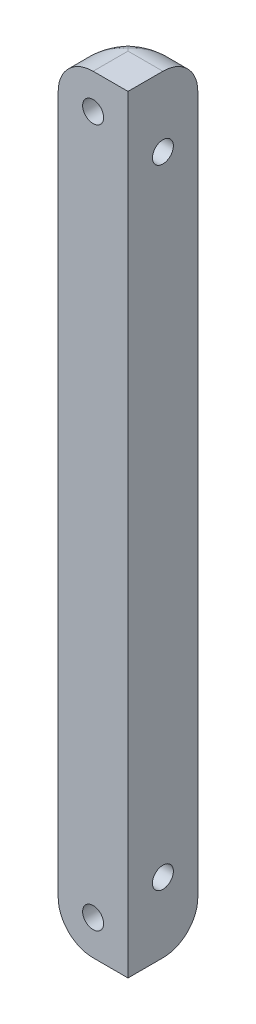
SolidWorks part; units mm, degrees
ref_plane "Front Plane" through (0, 0, 0) normal (0, 0, 1) x (1, 0, 0)
ref_plane "Top Plane" through (0, 0, 0) normal (0, 1, 0) x (1, 0, 0)
ref_plane "Right Plane" through (0, 0, 0) normal (1, 0, 0) x (0, 0, -1)
sketch "Sketch1" plane through (0, 0, 0) normal (0, 1, 0) x (1, 0, 0)
  line L1 (-6.35, -6.35) -> (6.35, -6.35)
  line L2 (-6.35, -6.35) -> (-6.35, 6.35)
  line L3 (-6.35, 6.35) -> (6.35, 6.35)
  line L4 (6.35, -6.35) -> (6.35, 6.35)
  line L5 (-6.35, -6.35) -> (6.35, 6.35) construction
  line L6 (-6.35, 6.35) -> (6.35, -6.35) construction
  point P0 (0, 0)
  dimension "D1" = 12.7
  dimension "D2" = 12.7
extrude "Boss-Extrude1" add sketch "Sketch1" along normal blind 139.7
sketch "Sketch2" plane through (0, 0, 6.35) normal (0, 0, 1) x (1, 0, 0)
  line L0 (-6.35, 0) -> (6.35, 0) construction
  line L1 (-6.35, 139.7) -> (6.35, 139.7) construction
  circle A0 centre (0, 6.35) radius 1.905
  circle A1 centre (0, 133.35) radius 1.905
  point P4 (0, 0)
  dimension "D1" = 3.81
  dimension "D2" = 6.35
  dimension "D3" = 6.35
extrude "Cut-Extrude1" cut sketch "Sketch2" against normal through all
sketch "Sketch3" plane through (6.35, 0, 0) normal (1, 0, 0) x (0, 0, -1)
  line L0 (-6.35, 0) -> (6.35, 0) construction
  line L1 (-6.35, 139.7) -> (6.35, 139.7) construction
  circle A0 centre (0, 127) radius 1.905
  circle A1 centre (0, 12.7) radius 1.905
  point P4 (0, 0)
  dimension "D3" = 3.81
  dimension "D1" = 12.7
  dimension "D2" = 12.7
extrude "Cut-Extrude2" cut sketch "Sketch3" against normal through all
chamfer "Chamfer1" distance 9.525 angle 45 1 edges at (-6.35, 69.85, -6.35)
fillet "Fillet1" radius 6.35 4 edges at (4.7625, 0, -6.35) (-6.35, 0, 4.7625) (4.7625, 139.7, -6.35) (-6.35, 139.7, 4.7625)
fillet "Fillet2" radius 1.5875 6 edges at (-5.0201, 137.2386, 1.8451) (-5.0201, 2.4614, 1.8451) (-6.35, 69.85, 3.175) (1.8451, 2.4614, -5.0201) (1.8451, 137.2386, -5.0201) (3.175, 69.85, -6.35)
